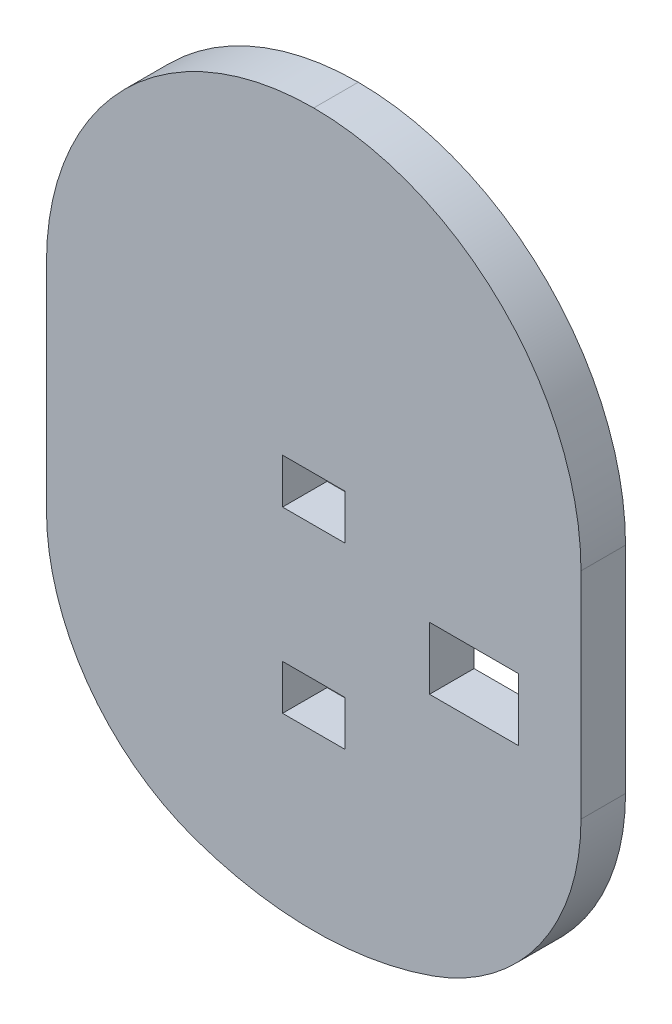
SolidWorks part; units mm, degrees
material "Acrylic (Medium-high impact)"
ref_plane "Front Plane" through (0, 0, 0) normal (0, 0, 1) x (1, 0, 0)
ref_plane "Top Plane" through (0, 0, 0) normal (0, 1, 0) x (1, 0, 0)
ref_plane "Right Plane" through (0, 0, 0) normal (1, 0, 0) x (0, 0, -1)
sketch "Sketch1" plane through (0, 0, 0) normal (0, 0, 1) x (1, 0, 0)
  circle A0 centre (0, 0) radius 40
  point P0 (0, 0)
  dimension "D1" = 80
extrude "Boss-Extrude1" add sketch "Sketch1" along normal blind 5
sketch "Sketch10" plane through (0, 0, 5) normal (0, 0, 1) x (1, 0, 0)
  line L0 (-30, 26.4575) -> (-30, -26.4575)
  line L1 (30, 26.4575) -> (30, -26.4575)
  arc A0 (30, -26.4575) -> (30, 26.4575) centre (0, 0) ccw
  circle A1 centre (0, 0) radius 40
  arc A2 (-30, 26.4575) -> (-30, -26.4575) centre (0, 0) ccw
  dimension "D2" = 30
  dimension "D3" = 60
  dimension "D1" = 0
extrude "Cut-Extrude3" cut sketch "Sketch10" against normal blind 10
fillet "Fillet1" radius 30 2 edges at (-30, 26.4575, 2.5) (30, 26.4575, 2.5)
fillet "Fillet2" radius 25 2 edges at (-30, -26.4575, 2.5) (30, -26.4575, 2.5)
sketch "Sketch14" plane through (0, 0, 5) normal (0, 0, 1) x (1, 0, 0)
  line L1 (-3.5, 4.5) -> (3.5, 4.5)
  line L2 (-3.5, 4.5) -> (-3.5, -0.55)
  line L3 (-3.5, -0.55) -> (3.5, -0.55)
  line L4 (3.5, 4.5) -> (3.5, -0.55)
  line L5 (-3.5, 4.5) -> (3.5, -0.55) construction
  line L6 (-3.5, -0.55) -> (3.5, 4.5) construction
  line L7 (-3.5, -15.55) -> (3.5, -15.55)
  line L8 (-3.5, -15.55) -> (-3.5, -20.6)
  line L9 (-3.5, -20.6) -> (3.5, -20.6)
  line L10 (3.5, -15.55) -> (3.5, -20.6)
  line L11 (-3.5, -15.55) -> (3.5, -20.6) construction
  line L12 (-3.5, -20.6) -> (3.5, -15.55) construction
  point P0 (0, 1.975)
  point P5 (0, -18.075)
  point P10 (0, -0.55)
  dimension "D1" = 5.05
  dimension "D2" = 7
  dimension "D3" = 15
  dimension "D4" = 35.5
extrude "Cut-Extrude4" cut sketch "Sketch14" against normal blind 10
sketch "Sketch4" plane through (0, 0, 5) normal (0, 0, 1) x (1, 0, 0)
  line L1 (-11, 4.5) -> (11, 4.5)
  line L2 (-11, 4.5) -> (-11, -0.5)
  line L3 (-11, -0.5) -> (11, -0.5)
  line L4 (11, 4.5) -> (11, -0.5)
  line L5 (-11, 4.5) -> (11, -0.5) construction
  line L6 (-11, -0.5) -> (11, 4.5) construction
  point P0 (0, 2)
  dimension "D1" = 22
  dimension "D2" = 5
  dimension "D3" = 2
extrude "Boss-Extrude2" [suppressed] add sketch "Sketch4" along normal blind 35
sketch "Sketch5" [suppressed] plane through (0, 4.5, 0) normal (0, 1, 0) x (1, 0, 0)
  line L1 (-6, -11) -> (6, -11)
  line L2 (-6, -11) -> (-6, -34)
  line L3 (-6, -34) -> (6, -34)
  line L4 (6, -11) -> (6, -34)
  line L5 (-6, -11) -> (6, -34) construction
  line L6 (-6, -34) -> (6, -11) construction
  line L7 (-11, -40) -> (-11, -5) construction
  line L8 (11, -40) -> (-11, -40) construction
  point P0 (0, -22.5)
  point P10 (-11, -22.5)
  point P12 (0, -40)
  dimension "D1" = 12
  dimension "D2" = 23
extrude "Cut-Extrude1" [suppressed] cut sketch "Sketch5" against normal blind 5
sketch "Sketch6" [suppressed] plane through (0, 4.5, 0) normal (0, 1, 0) x (1, 0, 0)
  line L0 (0, -8) -> (0, -37) construction
  line L1 (-6, -11) -> (-6, -34) construction
  line L2 (-6, -34) -> (6, -34) construction
  circle A0 centre (0, -8) radius 1.25
  circle A1 centre (0, -37) radius 1.25
  point P4 (0, -22.5)
  point P7 (-6, -22.5)
  point P10 (0, -34)
  dimension "D1" = 2.5
  dimension "D2" = 29
extrude "Cut-Extrude2" [suppressed] cut sketch "Sketch6" against normal blind 5
sketch "Sketch7" [suppressed] plane through (0, 0, 40) normal (0, 0, 1) x (1, 0, 0)
  line L0 (11, -0.5) -> (11, 4.5) construction
  line L1 (-11, 4.5) -> (11, 4.5)
  line L2 (-11, 4.5) -> (-11, -15.5)
  line L3 (-11, -15.5) -> (11, -15.5)
  line L4 (11, 4.5) -> (11, -15.5)
  line L5 (11, -0.5) -> (11, 4.5) construction
  dimension "D1" = 20
extrude "Boss-Extrude3" [suppressed] add sketch "Sketch7" along normal blind 5
sketch "Sketch8" [suppressed] plane through (0, -15.5, 0) normal (0, -1, 0) x (1, 0, 0)
  line L1 (-11, 45) -> (11, 45)
  line L2 (-11, 45) -> (-11, 5)
  line L3 (-11, 5) -> (11, 5)
  line L4 (11, 45) -> (11, 5)
extrude "Boss-Extrude4" [suppressed] add sketch "Sketch8" along normal blind 5
sketch "Sketch9" [suppressed] plane through (0, -20.5, 0) normal (0, -1, 0) x (1, 0, 0)
  line L0 (-11, 5) -> (11, 5) construction
  circle A0 centre (0, 27.5) radius 3.75
  dimension "D1" = 7.5
  dimension "D2" = 22.5
extrude "Boss-Extrude5" [suppressed] add sketch "Sketch9" along normal blind 7
fillet "Fillet3" [suppressed] radius 0.5
fillet "Fillet4" [suppressed] radius 0.5
sketch "Sketch16" plane through (0, 0, 0) normal (0, 0, -1) x (-1, 0, 0)
  line L0 (14.1683, 36.4609) -> (18.4984, 33.9609)
  line L1 (14.1683, 36.4609) -> (9.9183, 29.0997)
  line L2 (9.9183, 29.0997) -> (14.2484, 26.5997)
  line L3 (14.2484, 26.5997) -> (18.4984, 33.9609)
  line L4 (14.1683, 36.4609) -> (19.9024, 36.4609) construction
  arc A0 (30, 10) -> (0, 40) centre (0, 10) ccw construction
  dimension "D1" = 5
  dimension "D2" = 8.5
  dimension "D3" = 30
extrude "Cut-Extrude5" [suppressed] cut sketch "Sketch16" against normal blind 1
sketch "Sketch18" plane through (0, 0, 0) normal (0, 0, -1) x (-1, 0, 0)
  line L0 (-30, 10) -> (-30, -14.1421) construction
  line L1 (-23, -3.5) -> (-13, -3.5)
  line L2 (-23, -3.5) -> (-23, -10.5)
  line L3 (-23, -10.5) -> (-13, -10.5)
  line L4 (-13, -3.5) -> (-13, -10.5)
  line L5 (-3.5, 4.5) -> (3.5, 4.5) construction
  dimension "D1" = 7
  dimension "D2" = 10
  dimension "D3" = 7
  dimension "D4" = 8
extrude "Cut-Extrude6" cut sketch "Sketch18" against normal blind 10
sketch "Sketch20" plane through (0, 0, 0) normal (0, 0, -1) x (-1, 0, 0)
  line L1 (-17.5, 20) -> (17.5, 20)
  line L2 (-17.5, 20) -> (-17.5, -20)
  line L3 (-17.5, -20) -> (17.5, -20)
  line L4 (17.5, 20) -> (17.5, -20)
  circle A0 centre (-17.5, 20) radius 8.5
  circle A1 centre (17.5, 20) radius 8.5
  circle A2 centre (17.5, -20) radius 8.5
  circle A3 centre (-17.5, -20) radius 8.5
  point P5 (-17.5, 0)
  point P6 (0, 20)
  dimension "D3" = 17
  dimension "D1" = 35
  dimension "D2" = 40
extrude "Cut-Extrude8" cut sketch "Sketch20" against normal blind 1 contours A1 | A2 | A3 | A0
